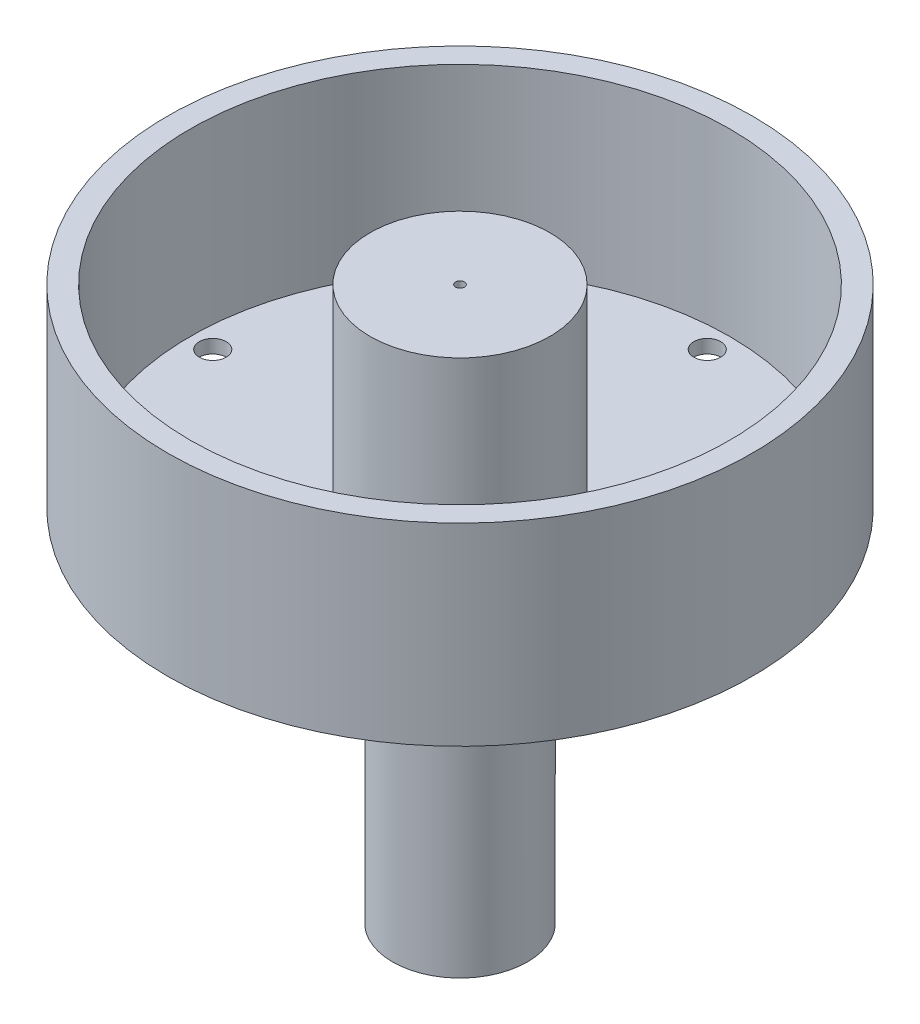
SolidWorks part; units mm, degrees
ref_plane "Front Plane" through (0, 0, 0) normal (0, 0, 1) x (1, 0, 0)
ref_plane "Top Plane" through (0, 0, 0) normal (0, 1, 0) x (1, 0, 0)
ref_plane "Right Plane" through (0, 0, 0) normal (1, 0, 0) x (0, 0, -1)
sketch "Sketch1" plane through (0, 0, 0) normal (0, 1, 0) x (1, 0, 0)
  circle A0 centre (0, 0) radius 65
  dimension "D1" = 130
extrude "Boss-Extrude1" add sketch "Sketch1" along normal blind 3
sketch "Sketch2" plane through (0, 3, 0) normal (0, 1, 0) x (1, 0, 0)
  circle A0 centre (0, 0) radius 55 construction
  circle A1 centre (0, 55) radius 3
  dimension "D1" = 110
  dimension "D2" = 6
extrude "Cut-Extrude1" cut sketch "Sketch2" against normal through all
pattern_circular "CirPattern1" count 4 over 360 about axis through (0, 3, 0) along (0, 1, 0) of "Cut-Extrude1"
sketch "Sketch3" plane through (0, 3, 0) normal (0, 1, 0) x (1, 0, 0)
  circle A0 centre (0, 0) radius 65 construction
  circle A1 centre (0, 0) radius 65
  circle A2 centre (0, 0) radius 60
  dimension "D1" = 5
extrude "Boss-Extrude2" add sketch "Sketch3" along normal blind 40
sketch "Sketch4" plane through (0, 3, 0) normal (0, 1, 0) x (1, 0, 0)
  circle A1 centre (0, 0) radius 20
  dimension "D2" = 40
extrude "Boss-Extrude3" add sketch "Sketch4" along normal blind 40
sketch "Sketch5" plane through (0, 0, 0) normal (0, -1, 0) x (1, 0, 0)
  circle A0 centre (0, 0) radius 10
  dimension "D1" = 20
extrude "Cut-Extrude2" cut sketch "Sketch5" against normal blind 30
sketch "Sketch6" plane through (0, 43, 0) normal (0, 1, 0) x (1, 0, 0)
  circle A0 centre (0, 0) radius 1
  dimension "D1" = 2
extrude "Cut-Extrude3" cut sketch "Sketch6" against normal through all
sketch "草圖1" plane through (0, 0, 0) normal (0, -1, 0) x (1, 0, 0)
  circle A1 centre (0, 0) radius 10 construction
  circle A2 centre (0, 0) radius 10
  circle A3 centre (0, 0) radius 15
  dimension "D1" = 30
extrude "填料-伸長1" add sketch "草圖1" along normal blind 80
